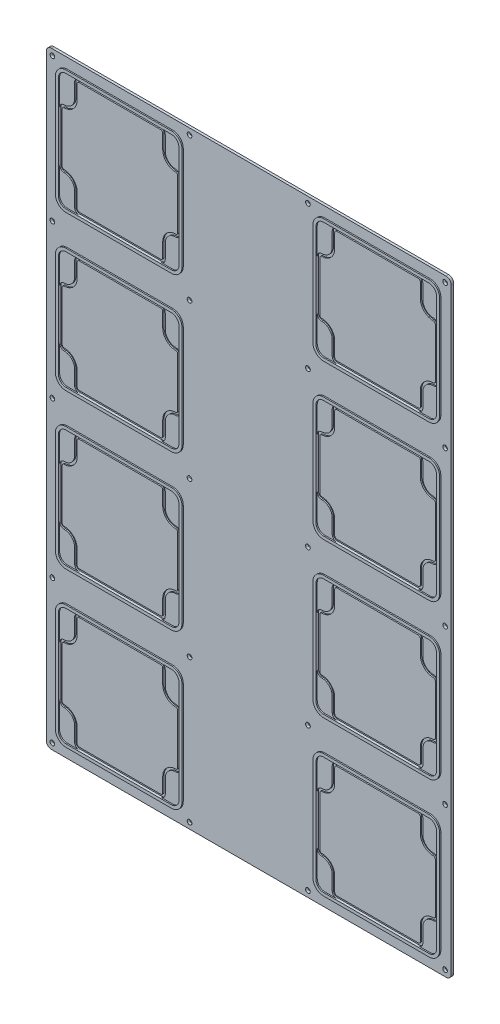
SolidWorks part; units mm, degrees
ref_plane "Front Plane" through (0, 0, 0) normal (0, 0, 1) x (1, 0, 0)
ref_plane "Top Plane" through (0, 0, 0) normal (0, 1, 0) x (1, 0, 0)
ref_plane "Right Plane" through (0, 0, 0) normal (1, 0, 0) x (0, 0, -1)
sketch "Sketch1" plane through (0, 0, 0) normal (0, 0, 1) x (1, 0, 0)
  line L1 (0, 0) -> (254, 0)
  line L2 (0, 0) -> (0, 381)
  line L3 (0, 381) -> (254, 381)
  line L4 (254, 0) -> (254, 381)
  dimension "D1" = 381
  dimension "D2" = 254
extrude "Boss-Extrude1" add sketch "Sketch1" along normal blind 1.5875
sketch "Sketch2" plane through (0, 0, 1.5875) normal (0, 0, 1) x (1, 0, 0)
  line L0 (89.8652, 377.19) -> (89.8652, 3.81) construction
  line L1 (0, 381) -> (254, 381) construction
  line L2 (127, 381) -> (127, 377.19) construction
  line L3 (3.81, 377.19) -> (250.19, 377.19) construction
  line L5 (164.1348, 377.19) -> (164.1348, 3.81) construction
  line L6 (3.81, 377.19) -> (3.81, 3.81) construction
  line L7 (3.81, 3.81) -> (250.19, 3.81) construction
  line L8 (250.19, 3.81) -> (250.19, 377.19) construction
  line L9 (3.81, 190.5) -> (250.19, 190.5) construction
  line L10 (3.81, 287.3756) -> (250.19, 287.3756) construction
  line L11 (3.81, 93.6244) -> (250.19, 93.6244) construction
  line L12 (0, 381) -> (0, 0) construction
  line L13 (0, 190.5) -> (3.81, 190.5) construction
  circle A0 centre (3.81, 377.19) radius 1.4732
  circle A1 centre (89.8652, 377.19) radius 1.4732
  circle A2 centre (164.1348, 377.19) radius 1.4732
  circle A3 centre (250.19, 377.19) radius 1.4732
  circle A4 centre (164.1348, 287.3755) radius 1.4732
  circle A5 centre (3.81, 287.3756) radius 1.4732
  circle A6 centre (250.19, 287.3756) radius 1.4732
  circle A7 centre (89.8652, 287.3756) radius 1.4732
  circle A8 centre (164.1348, 190.5) radius 1.4732
  circle A9 centre (3.81, 191.135) radius 1.4732
  circle A10 centre (250.19, 190.5) radius 1.4732
  circle A11 centre (89.8652, 190.5) radius 1.4732
  circle A12 centre (164.1348, 93.6244) radius 1.4732
  circle A13 centre (3.81, 93.6244) radius 1.4732
  circle A14 centre (250.19, 93.6244) radius 1.4732
  circle A15 centre (89.8652, 93.6244) radius 1.4732
  circle A16 centre (164.1348, 3.81) radius 1.4732
  circle A17 centre (3.81, 3.81) radius 1.4732
  circle A18 centre (250.19, 3.81) radius 1.4732
  circle A19 centre (89.8652, 3.81) radius 1.4732
  dimension "D6" = 2.9464
  dimension "D23" = 0
  dimension "D24" = 0
  dimension "D25" = 0
  dimension "D28" = 0
  dimension "D29" = 0
  dimension "D30" = 0
  dimension "D31" = 0
  dimension "D32" = 86.0552
  dimension "D1" = 246.38
  dimension "D3" = 373.38
  dimension "D4" = 96.8756
  dimension "D5" = 96.8756
  dimension "D7" = 86.0552
  dimension "D8" = 86.0552
  dimension "D9" = 0
  dimension "D10" = 0
  dimension "D11" = 0
  dimension "D12" = 86.0552
  dimension "D13" = 0
  dimension "D14" = 0
  dimension "D15" = 0
  dimension "D16" = 0
  dimension "D17" = 0
  dimension "D18" = 0
  dimension "D19" = 0
  dimension "D20" = 0
  dimension "D21" = 0
  dimension "D22" = 0
  dimension "D26" = 0
  dimension "D27" = 0
extrude "Cut-Extrude1" cut sketch "Sketch2" against normal through all
fillet "Fillet1" radius 3.175 4 edges at (254, 0, 0.7937) (0, 0, 0.7937) (254, 381, 0.7937) (0, 381, 0.7937)
sketch "Sketch3" plane through (0, 0, 1.5875) normal (0, 0, 1) x (1, 0, 0)
  line L0 (9.9695, 45.1866) -> (46.2026, 45.1866) construction
  line L1 (46.2026, 45.1866) -> (46.2026, 9.9695) construction
  line L2 (81.2038, 28.3591) -> (82.4357, 28.3591) construction
  line L3 (82.4357, 29.591) -> (82.4357, 60.7822)
  line L4 (73.0377, 11.2014) -> (73.0377, 20.193)
  line L5 (81.2038, 62.0141) -> (82.4357, 62.0141) construction
  line L6 (71.8058, 9.9695) -> (20.5994, 9.9695)
  line L7 (19.3675, 11.2014) -> (19.3675, 20.193)
  line L8 (11.2014, 28.3591) -> (9.9695, 28.3591) construction
  line L9 (9.9695, 29.591) -> (9.9695, 60.7822)
  line L10 (73.0377, 79.1718) -> (73.0377, 70.1802)
  line L11 (71.8058, 80.4037) -> (20.5994, 80.4037)
  line L12 (3.175, 0) -> (250.825, 0) construction
  line L13 (0, 377.825) -> (0, 3.175) construction
  line L14 (11.2014, 62.0141) -> (9.9695, 62.0141) construction
  line L15 (19.3675, 79.1718) -> (19.3675, 70.1802)
  line L16 (17.78, 79.1718) -> (17.78, 70.1802)
  line L17 (8.382, 29.591) -> (8.382, 60.7822)
  line L18 (17.78, 11.2014) -> (17.78, 20.193)
  line L19 (71.8058, 8.382) -> (20.5994, 8.382)
  line L20 (74.6252, 11.2014) -> (74.6252, 20.193)
  line L21 (84.0232, 29.591) -> (84.0232, 60.7822)
  line L22 (74.6252, 79.1718) -> (74.6252, 70.1802)
  line L23 (71.8058, 81.9912) -> (20.5994, 81.9912)
  arc A0 (19.3675, 20.193) -> (11.2014, 28.3591) centre (11.2014, 20.193) ccw
  arc A1 (9.9695, 29.591) -> (11.2014, 28.3591) centre (11.2014, 29.591) ccw
  arc A2 (19.3675, 11.2014) -> (20.5994, 9.9695) centre (20.5994, 11.2014) ccw
  arc A3 (73.0377, 11.2014) -> (71.8058, 9.9695) centre (71.8058, 11.2014) cw
  arc A4 (82.4357, 29.591) -> (81.2038, 28.3591) centre (81.2038, 29.591) cw
  arc A5 (73.0377, 20.193) -> (81.2038, 28.3591) centre (81.2038, 20.193) cw
  arc A6 (73.0377, 70.1802) -> (81.2038, 62.0141) centre (81.2038, 70.1802) ccw
  arc A7 (82.4357, 60.7822) -> (81.2038, 62.0141) centre (81.2038, 60.7822) ccw
  arc A8 (73.0377, 79.1718) -> (71.8058, 80.4037) centre (71.8058, 79.1718) ccw
  arc A9 (19.3675, 79.1718) -> (20.5994, 80.4037) centre (20.5994, 79.1718) cw
  arc A10 (9.9695, 60.7822) -> (11.2014, 62.0141) centre (11.2014, 60.7822) cw
  arc A11 (19.3675, 70.1802) -> (11.2014, 62.0141) centre (11.2014, 70.1802) cw
  arc A12 (17.78, 70.1802) -> (11.2014, 63.6016) centre (11.2014, 70.1802) cw
  arc A13 (8.382, 60.7822) -> (11.2014, 63.6016) centre (11.2014, 60.7822) cw
  arc A14 (8.382, 29.591) -> (11.2014, 26.7716) centre (11.2014, 29.591) ccw
  arc A15 (17.78, 20.193) -> (11.2014, 26.7716) centre (11.2014, 20.193) ccw
  arc A16 (17.78, 11.2014) -> (20.5994, 8.382) centre (20.5994, 11.2014) ccw
  arc A17 (74.6252, 11.2014) -> (71.8058, 8.382) centre (71.8058, 11.2014) cw
  arc A18 (74.6252, 20.193) -> (81.2038, 26.7716) centre (81.2038, 20.193) cw
  arc A19 (84.0232, 29.591) -> (81.2038, 26.7716) centre (81.2038, 29.591) cw
  arc A20 (84.0232, 60.7822) -> (81.2038, 63.6016) centre (81.2038, 60.7822) ccw
  arc A21 (74.6252, 70.1802) -> (81.2038, 63.6016) centre (81.2038, 70.1802) ccw
  arc A22 (74.6252, 79.1718) -> (71.8058, 81.9912) centre (71.8058, 79.1718) ccw
  arc A23 (17.78, 79.1718) -> (20.5994, 81.9912) centre (20.5994, 79.1718) cw
  point P35 (82.4357, 45.1866)
  dimension "D6" = 8.1661
  dimension "D7" = 2.4638
  dimension "D8" = 1.2319
  dimension "D1" = 9.9695
  dimension "D2" = 9.9695
  dimension "D3" = 19.3675
  dimension "D4" = 28.3591
  dimension "D5" = 45.1866
  dimension "D10" = 46.2026
  dimension "D9" = 1.5875
extrude "Cut-Extrude2" cut sketch "Sketch3" against normal blind 0.7937
sketch "Sketch4" plane through (0, 0, 1.5875) normal (0, 0, 1) x (1, 0, 0)
  line L0 (8.382, 60.7822) -> (8.382, 77.2287)
  line L1 (13.1445, 81.9912) -> (20.5994, 81.9912)
  line L2 (20.5994, 81.9912) -> (79.2607, 81.9912)
  line L3 (84.0232, 77.2287) -> (84.0232, 13.1445)
  line L4 (79.2607, 8.382) -> (13.1445, 8.382)
  line L5 (8.382, 13.1445) -> (8.382, 60.7822)
  line L6 (6.477, 60.7822) -> (6.477, 77.2287)
  line L7 (13.1445, 83.8962) -> (20.5994, 83.8962)
  line L8 (20.5994, 83.8962) -> (79.2607, 83.8962)
  line L9 (85.9282, 77.2287) -> (85.9282, 13.1445)
  line L10 (79.2607, 6.477) -> (13.1445, 6.477)
  line L11 (6.477, 13.1445) -> (6.477, 60.7822)
  arc A0 (13.1445, 81.9912) -> (8.382, 77.2287) centre (13.1445, 77.2287) ccw
  arc A1 (79.2607, 81.9912) -> (84.0232, 77.2287) centre (79.2607, 77.2287) cw
  arc A2 (84.0232, 13.1445) -> (79.2607, 8.382) centre (79.2607, 13.1445) cw
  arc A3 (8.382, 13.1445) -> (13.1445, 8.382) centre (13.1445, 13.1445) ccw
  arc A4 (13.1445, 83.8962) -> (6.477, 77.2287) centre (13.1445, 77.2287) ccw
  arc A5 (79.2607, 83.8962) -> (85.9282, 77.2287) centre (79.2607, 77.2287) cw
  arc A6 (85.9282, 13.1445) -> (79.2607, 6.477) centre (79.2607, 13.1445) cw
  arc A7 (6.477, 13.1445) -> (13.1445, 6.477) centre (13.1445, 13.1445) ccw
  dimension "D1" = 4.7625
  dimension "D2" = 1.905
extrude "Boss-Extrude2" add sketch "Sketch4" along normal blind 0.7937
pattern_linear "LPattern1" count 4 spacing 96.8756 along (0, 1, 0) count 2 spacing 161.5948 along (1, 0, 0) of "Cut-Extrude2", "Boss-Extrude2"
